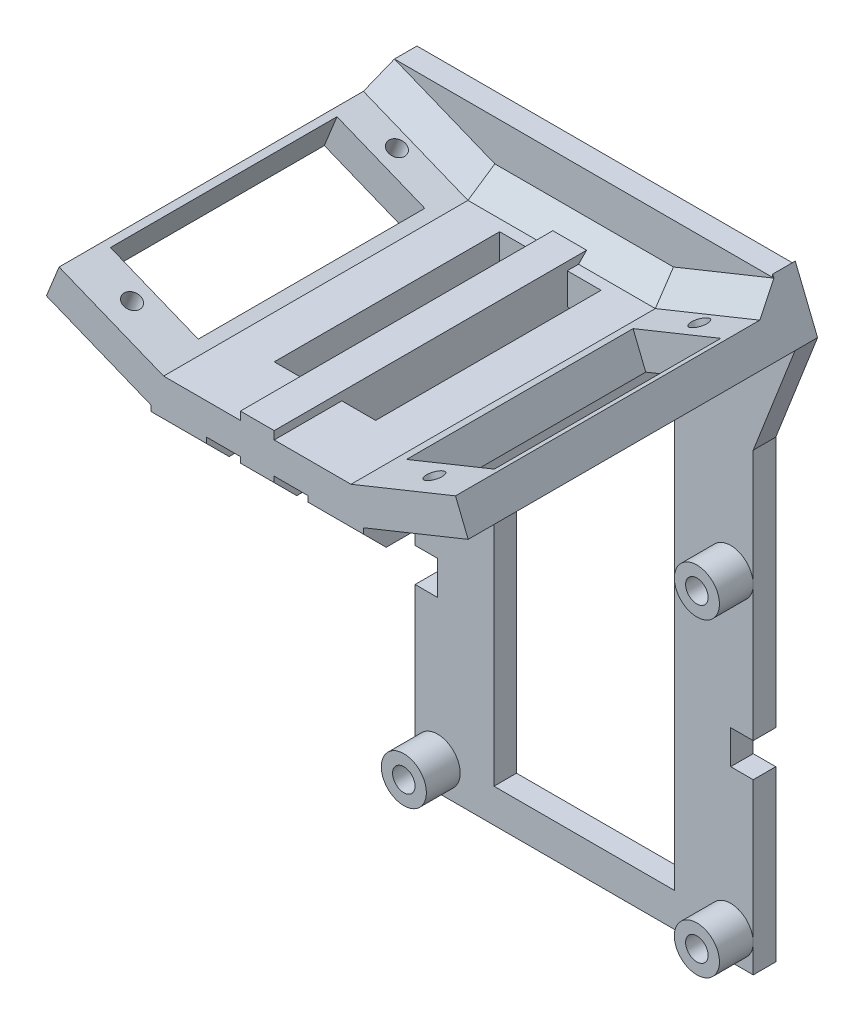
SolidWorks part; units mm, degrees
ref_plane "前基準面" through (0, 0, 0) normal (0, 0, 1) x (1, 0, 0)
ref_plane "上基準面" through (0, 0, 0) normal (0, 1, 0) x (1, 0, 0)
ref_plane "右基準面" through (0, 0, 0) normal (1, 0, 0) x (0, 0, -1)
sketch "草圖1" plane through (0, 0, 0) normal (0, 0, 1) x (1, 0, 0)
  line L0 (-15, 0) -> (15, 0)
  line L1 (-15, 0) -> (-15, -1)
  line L2 (18.7087, -10.1794) -> (15, -11.6779)
  line L3 (15, -11.6779) -> (15, -60)
  line L4 (15, -60) -> (-15, -60)
  line L5 (-15, -60) -> (-15, -11.6779)
  line L6 (-15, -11.6779) -> (-18.7087, -10.1794)
  line L7 (-15, -1) -> (-18.7087, -10.1794)
  line L8 (0, 15.1551) -> (0, -26.7536) construction
  line L9 (15, 0) -> (15, -1)
  line L10 (15, -1) -> (18.7087, -10.1794)
  dimension "D7" = 68
  dimension "D8" = 4
  dimension "D9" = 1
  dimension "D10" = 1
  dimension "D1" = 30
  dimension "D2" = 15
  dimension "D3" = 30
  dimension "D4" = 15
  dimension "D5" = 60
  dimension "D6" = 136
  dimension "D11" = 90
extrude "填料-伸長1" add sketch "草圖1" along normal blind 2
sketch "草圖2" plane through (0, 0, 2) normal (0, 0, 1) x (1, 0, 0)
  line L0 (0, 35.4377) -> (0, -39.094) construction
  line L2 (-18.7087, -10.1794) -> (-9.4369, -13.9255)
  line L3 (-9.4369, -13.9255) -> (9.4369, -13.9255)
  line L4 (9.4369, -13.9255) -> (18.7087, -10.1794)
  line L5 (15, -11.6779) -> (18.7087, -10.1794) construction
  line L6 (-18.7087, -10.1794) -> (-15, -11.6779) construction
  line L7 (-18.7087, -10.1794) -> (-17.5849, -7.3979)
  line L8 (-15, -1) -> (-18.7087, -10.1794) construction
  line L9 (-17.5849, -7.3979) -> (-8.3131, -11.144)
  line L10 (-8.3131, -11.144) -> (8.3131, -11.144)
  line L11 (8.3131, -11.144) -> (17.5849, -7.3979)
  line L12 (18.7087, -10.1794) -> (15, -1) construction
  line L13 (17.5849, -7.3979) -> (18.7087, -10.1794)
  dimension "D1" = 10
  dimension "D2" = 3
  dimension "D3" = 3
  dimension "D4" = 10
  dimension "D5" = 10
extrude "填料-伸長2" add sketch "草圖2" along normal blind 29 and the other way blind 2
sketch "草圖3" plane through (4.9147, -15.7526, 0) normal (-0.3746, 0.9272, 0) x (0.9272, 0.3746, 0)
  line L1 (14.8774, -31) -> (4.8774, -31) construction
  line L2 (14.8774, -2) -> (14.8774, -31) construction
  line L5 (14.8774, -6.9) -> (5.8774, -6.9)
  line L6 (14.8774, -6.9) -> (14.8774, -27)
  line L7 (14.8774, -27) -> (5.8774, -27)
  line L8 (5.8774, -6.9) -> (5.8774, -27)
  circle A2 centre (10.3774, -5.2) radius 0.75
  circle A3 centre (10.3774, -28.7) radius 0.75
  dimension "D7" = 1.5
  dimension "D2" = 20.1
  dimension "D3" = 9
  dimension "D4" = 23.5
  dimension "D5" = 1.7
  dimension "D6" = 4
  dimension "D11" = 4.5
extrude "除料-伸長5" cut sketch "草圖3" along normal up to next
sketch "草圖12" plane through (-6.161, -15.249, 0) normal (-0.3746, -0.9272, 0) x (0.9272, -0.3746, 0)
  line L0 (-13.5332, 31) -> (-13.5332, 0) construction
  line L1 (-13.5332, 27) -> (-4.5332, 27)
  line L2 (-13.5332, 27) -> (-13.5332, 6.9)
  line L3 (-13.5332, 6.9) -> (-4.5332, 6.9)
  line L4 (-4.5332, 27) -> (-4.5332, 6.9)
  line L5 (-13.5332, 31) -> (-3.5332, 31) construction
  circle A0 centre (-9.0332, 28.7) radius 0.75
  circle A1 centre (-9.0332, 5.2) radius 0.75
  dimension "D7" = 1.5
  dimension "D8" = 1.5
  dimension "D1" = 9
  dimension "D2" = 20.1
  dimension "D3" = 4
  dimension "D4" = 23.5
  dimension "D5" = 1.7
  dimension "D6" = 4.5
extrude "除料-伸長7" cut sketch "草圖12" against normal up to next
sketch "草圖13" plane through (0, 0, 2) normal (0, 0, 1) x (1, 0, 0)
  line L0 (-15, -11.6779) -> (-15, -60) construction
  line L1 (-15, -60) -> (15, -60) construction
  line L2 (-9.4369, -13.9255) -> (9.4369, -13.9255) construction
  line L3 (-8, -18.9255) -> (8, -18.9255)
  line L4 (-8, -18.9255) -> (-8, -57)
  line L5 (-8, -57) -> (8, -57)
  line L6 (8, -18.9255) -> (8, -57)
  line L7 (-8, -18.9255) -> (8, -57) construction
  line L8 (-8, -57) -> (8, -18.9255) construction
  line L9 (-13, -42) -> (-15, -42)
  line L10 (-13, -42) -> (-13, -45)
  line L11 (-13, -45) -> (-15, -45)
  line L12 (-15, -42) -> (-15, -45)
  line L13 (-13, -42) -> (-15, -45) construction
  line L14 (-13, -45) -> (-15, -42) construction
  line L15 (15, -60) -> (15, -11.6779) construction
  line L16 (13, -42) -> (15, -42)
  line L17 (13, -42) -> (13, -45)
  line L18 (13, -45) -> (15, -45)
  line L19 (15, -42) -> (15, -45)
  line L20 (13, -42) -> (15, -45) construction
  line L21 (13, -45) -> (15, -42) construction
  circle A0 centre (-13, -30) radius 1
  circle A1 centre (13, -30) radius 1
  circle A2 centre (-13, -57.5) radius 1
  circle A3 centre (13, -57.5) radius 1
  point P11 (0, -37.9628)
  point P18 (-14, -43.5)
  point P25 (14, -43.5)
  dimension "D4" = 2
  dimension "D5" = 2
  dimension "D6" = 2
  dimension "D7" = 2
  dimension "D12" = 3
  dimension "D1" = 26
  dimension "D2" = 27.5
  dimension "D3" = 2.5
  dimension "D8" = 13
  dimension "D9" = 16
  dimension "D10" = 3
  dimension "D11" = 5
  dimension "D13" = 3
  dimension "D14" = 2
  dimension "D15" = 2
  dimension "D16" = 14
extrude "除料-伸長8" cut sketch "草圖13" against normal up to next
chamfer "導角4" distance 1 angle 45 2 edges at (-15, 0, 1) (15, 0, 1)
chamfer "導角5" distance 2 angle 45 3 edges at (12.949, -9.2709, 2) (0, -11.144, 2) (-12.949, -9.2709, 2)
sketch "草圖14" plane through (0, 0, 31) normal (0, 0, 1) x (1, 0, 0)
  line L1 (-1.5, -16.4255) -> (1.5, -16.4255)
  line L2 (-1.5, -16.4255) -> (-1.5, -10.4255)
  line L3 (-1.5, -10.4255) -> (1.5, -10.4255)
  line L4 (1.5, -16.4255) -> (1.5, -10.4255)
  line L5 (-1.5, -16.4255) -> (1.5, -10.4255) construction
  line L6 (-1.5, -10.4255) -> (1.5, -16.4255) construction
  line L7 (9.4369, -13.9255) -> (-9.4369, -13.9255) construction
  line L8 (-9.4369, -13.9255) -> (-4.5, -13.9255)
  line L9 (-9.4369, -13.9255) -> (-9.4369, -16.4255)
  line L10 (-9.4369, -16.4255) -> (-4.5, -16.4255)
  line L11 (-4.5, -13.9255) -> (-4.5, -16.4255)
  line L12 (9.4369, -13.9255) -> (4.5, -13.9255)
  line L13 (9.4369, -13.9255) -> (9.4369, -16.4255)
  line L14 (9.4369, -16.4255) -> (4.5, -16.4255)
  line L15 (4.5, -13.9255) -> (4.5, -16.4255)
  point P0 (0, -13.4255)
  dimension "D1" = 6
  dimension "D2" = 3
  dimension "D3" = 2.5
  dimension "D4" = 3
  dimension "D5" = 3
extrude "填料-伸長8" add sketch "草圖14" against normal up to surface (29 mm away) up to face at (0, -37.9628, 2)
chamfer "導角6" distance 2 angle 45 3 edges at (0, -16.4255, 31) (6.9684, -16.4255, 31) (-6.9684, -16.4255, 31)
sketch "草圖15" plane through (0, 0, 2) normal (0, 0, 1) x (1, 0, 0)
  circle A0 centre (-13, -30) radius 1
  circle A1 centre (-13, -30) radius 2
  circle A2 centre (13, -30) radius 1
  circle A3 centre (13, -30) radius 2
  circle A4 centre (13, -57.5) radius 1
  circle A5 centre (13, -57.5) radius 2
  circle A6 centre (-13, -57.5) radius 1
  circle A7 centre (-13, -57.5) radius 2
extrude "填料-伸長9" add sketch "草圖15" along normal blind 3
sketch "草圖16" plane through (0, -13.9255, 0) normal (0, -1, 0) x (1, 0, 0)
  line L0 (-1.5, 2) -> (-1.5, 29) construction
  line L1 (-1.5, 25) -> (-4.5, 25)
  line L2 (-1.5, 25) -> (-1.5, 5)
  line L3 (-1.5, 5) -> (-4.5, 5)
  line L4 (-4.5, 25) -> (-4.5, 5)
  line L5 (1.5, 2) -> (1.5, 31) construction
  line L6 (1.5, 25) -> (4.5, 25)
  line L7 (1.5, 25) -> (1.5, 5)
  line L8 (1.5, 5) -> (4.5, 5)
  line L9 (4.5, 25) -> (4.5, 5)
  dimension "D1" = 3
  dimension "D2" = 3
  dimension "D3" = 20
  dimension "D4" = 20
  dimension "D5" = 5
  dimension "D6" = 5
extrude "除料-伸長9" cut sketch "草圖16" against normal up to next
sketch "草圖17" plane through (0, 0, 0) normal (0, 0, -1) x (-1, 0, 0)
  line L0 (-18.7087, -10.1794) -> (-15, -19.6779)
  line L1 (-15, -60) -> (-15, -45) construction
  line L2 (-15, -19.6779) -> (-15, -11.6779)
  line L3 (-15, -11.6779) -> (-18.7087, -10.1794)
  line L4 (18.7087, -10.1794) -> (15, -11.6779)
  line L5 (15, -11.6779) -> (15, -19.6779)
  line L6 (15, -11.6779) -> (15, -42) construction
  line L7 (15, -19.6779) -> (18.7087, -10.1794)
  dimension "D1" = 8
extrude "填料-伸長10" add sketch "草圖17" against normal up to surface (2 mm away) up to face at (0, -37.9628, 2)
sketch "草圖18" plane through (0, 0, 31) normal (0, 0, 1) x (1, 0, 0)
  line L0 (-17.5849, -7.3979) -> (-18.7087, -10.1794)
  line L1 (-18.7087, -10.1794) -> (-18.1524, -10.4042)
  line L2 (-18.7087, -10.1794) -> (-9.4369, -13.9255) construction
  line L3 (-18.1524, -10.4042) -> (-17.0286, -7.6227)
  line L4 (-8.3131, -11.144) -> (-17.5849, -7.3979) construction
  line L5 (-17.0286, -7.6227) -> (-17.5849, -7.3979)
  line L7 (17.5849, -7.3979) -> (18.7087, -10.1794)
  line L8 (18.7087, -10.1794) -> (18.1524, -10.4042)
  line L9 (9.4369, -13.9255) -> (18.7087, -10.1794) construction
  line L10 (18.1524, -10.4042) -> (17.0286, -7.6227)
  line L11 (17.5849, -7.3979) -> (8.3131, -11.144) construction
  line L12 (17.0286, -7.6227) -> (17.5849, -7.3979)
  dimension "D1" = 0.6
  dimension "D2" = 0.6
extrude "填料-伸長11" add sketch "草圖18" against normal up to surface (24.1 mm away) up to face at (-13.9745, -10.4744, 6.9)
sketch "草圖20" plane through (0, 0, 2) normal (0, 0, 1) x (1, 0, 0)
  line L1 (-16.8357, -5.5435) -> (16.7306, -5.5435)
  line L2 (-16.8357, -5.5435) -> (-16.8357, 1.144)
  line L3 (-16.8357, 1.144) -> (16.7306, 1.144)
  line L4 (16.7306, -5.5435) -> (16.7306, 1.144)
extrude "除料-伸長11" cut sketch "草圖20" against normal up to next
